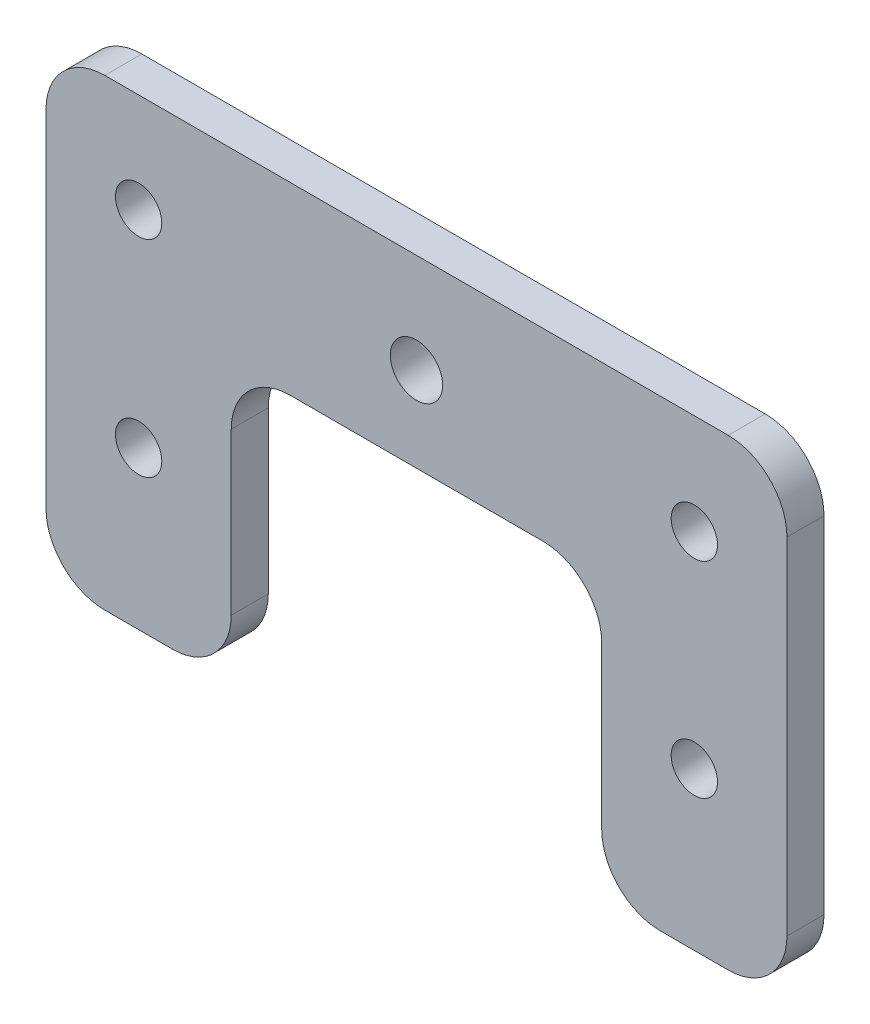
SolidWorks part; units mm, degrees
ref_plane "Alzado" through (0, 0, 0) normal (0, 0, 1) x (1, 0, 0)
ref_plane "Planta" through (0, 0, 0) normal (0, 1, 0) x (1, 0, 0)
ref_plane "Vista lateral" through (0, 0, 0) normal (1, 0, 0) x (0, 0, -1)
sketch "Croquis1" plane through (0, 0, 0) normal (0, 0, 1) x (1, 0, 0)
  line L1 (26.5381, 6.6994) -> (53.8381, 6.6994)
  line L2 (0.1881, 6.6044) -> (0.1881, 20.2544)
  line L3 (6.5381, 26.6044) -> (73.8381, 26.6044)
  line L4 (80.1881, 6.6044) -> (80.1881, 20.2544)
  line L6 (0.1881, 6.6044) -> (0.1881, -17.0456)
  line L7 (6.5381, -23.3956) -> (13.8381, -23.3956)
  line L8 (20.1881, 0.3494) -> (20.1881, -17.0456)
  line L13 (40.1881, 26.6044) -> (40.1881, -35.7819) construction
  line L14 (73.8381, -23.3956) -> (66.5381, -23.3956)
  line L15 (60.1881, 0.3494) -> (60.1881, -17.0456)
  line L16 (80.1881, 6.6044) -> (80.1881, -17.0456)
  circle A1 centre (10.1881, 15.8665) radius 2.5
  circle A2 centre (70.1881, 15.7714) radius 2.5
  circle A3 centre (10.1881, -6.3956) radius 2.5
  arc A5 (26.5381, 6.6994) -> (20.1881, 0.3494) centre (26.5381, 0.3494) ccw
  arc A6 (80.1881, 20.2544) -> (73.8381, 26.6044) centre (73.8381, 20.2544) ccw
  arc A7 (6.5381, 26.6044) -> (0.1881, 20.2544) centre (6.5381, 20.2544) ccw
  arc A8 (60.1881, 0.3494) -> (53.8381, 6.6994) centre (53.8381, 0.3494) ccw
  arc A9 (6.5381, -23.3956) -> (0.1881, -17.0456) centre (6.5381, -17.0456) cw
  arc A10 (13.8381, -23.3956) -> (20.1881, -17.0456) centre (13.8381, -17.0456) ccw
  circle A24 centre (40.1881, 15.8665) radius 2.8214
  arc A30 (73.8381, -23.3956) -> (80.1881, -17.0456) centre (73.8381, -17.0456) ccw
  arc A31 (66.5381, -23.3956) -> (60.1881, -17.0456) centre (66.5381, -17.0456) cw
  circle A32 centre (70.1881, -6.3956) radius 2.5
  point P22 (20.1881, 6.6994)
  point P25 (80.1881, 26.6044)
  point P28 (0.1881, 26.6044)
  point P31 (114.1981, 6.6994)
  point P34 (0.1881, -23.3956)
  point P37 (20.1881, -23.3956)
  dimension "D8" = 5
  dimension "D19" = 6.35
  dimension "D20" = 6.35
  dimension "D21" = 6.35
  dimension "D1" = 20
  dimension "D2" = 80
  dimension "D3" = 30
  dimension "D4" = 20
  dimension "D15" = 10
  dimension "D16" = 10
  dimension "D18" = 94.01
extrude "Saliente-Extruir1" add sketch "Croquis1" along normal blind 4 contours L3 L13 A24 L1 A8 L15 A31 L14 A30 L16 L4 A6 A32 A2 | L13 L3 A7 L2 L6 A9 L7 A10 L8 A5 L1 A24 A1 A3 region at (16.0382, 6.0625, 0) region at (64.3379, 6.0639, 0)
